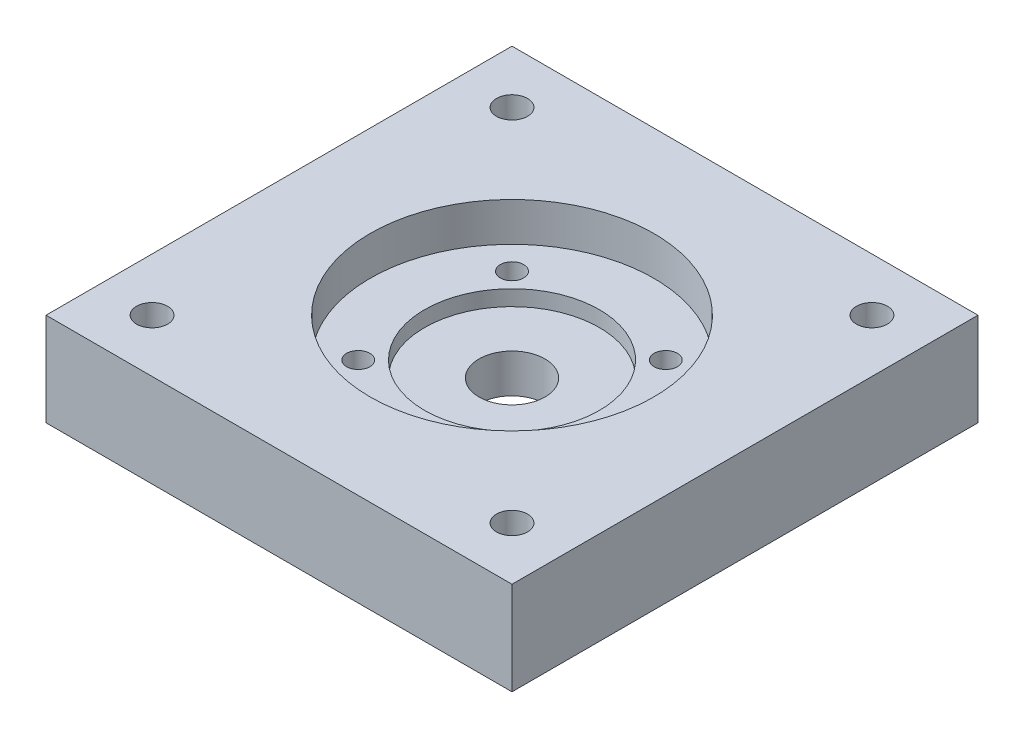
SolidWorks part; units mm, degrees
ref_plane "前视基准面" through (0, 0, 0) normal (0, 0, 1) x (1, 0, 0)
ref_plane "上视基准面" through (0, 0, 0) normal (0, 1, 0) x (1, 0, 0)
ref_plane "右视基准面" through (0, 0, 0) normal (1, 0, 0) x (0, 0, -1)
sketch "草图1" plane through (0, 0, 0) normal (0, 1, 0) x (1, 0, 0)
  line L0 (25.6208, 20.7218) -> (26.5174, 24.0679)
  line L1 (-21.05, 21.05) -> (21.05, 21.05)
  line L2 (-21.05, 21.05) -> (-21.05, -21.05)
  line L3 (-21.05, -21.05) -> (21.05, -21.05)
  line L4 (21.05, 21.05) -> (21.05, -21.05)
  line L5 (-21.05, 21.05) -> (21.05, -21.05) construction
  line L6 (-21.05, -21.05) -> (21.05, 21.05) construction
  line L7 (-30, 30) -> (30, 30)
  line L8 (-30, 30) -> (-30, -30)
  line L9 (-30, -30) -> (30, -30)
  line L10 (30, 30) -> (30, -30)
  line L11 (-30, 30) -> (30, -30) construction
  line L12 (-30, -30) -> (30, 30) construction
  line L13 (-20.7218, 25.6208) -> (-24.0679, 26.5174)
  line L14 (-24.0679, 26.5174) -> (-26.5174, 24.0679)
  line L15 (-26.5174, 24.0679) -> (-25.6208, 20.7218)
  line L16 (-25.6208, 20.7218) -> (-22.2747, 19.8253)
  line L17 (-22.2747, 19.8253) -> (-19.8253, 22.2747)
  line L18 (-19.8253, 22.2747) -> (-20.7218, 25.6208)
  line L19 (26.5174, 24.0679) -> (24.0679, 26.5174)
  line L20 (24.0679, 26.5174) -> (20.7218, 25.6208)
  line L21 (20.7218, 25.6208) -> (19.8253, 22.2747)
  line L22 (19.8253, 22.2747) -> (22.2747, 19.8253)
  line L23 (22.2747, 19.8253) -> (25.6208, 20.7218)
  line L24 (20.7218, -25.6208) -> (24.0679, -26.5174)
  line L25 (24.0679, -26.5174) -> (26.5174, -24.0679)
  line L26 (26.5174, -24.0679) -> (25.6208, -20.7218)
  line L27 (25.6208, -20.7218) -> (22.2747, -19.8253)
  line L28 (22.2747, -19.8253) -> (19.8253, -22.2747)
  line L29 (19.8253, -22.2747) -> (20.7218, -25.6208)
  line L30 (-25.6208, -20.7218) -> (-26.5174, -24.0679)
  line L31 (-26.5174, -24.0679) -> (-24.0679, -26.5174)
  line L32 (-24.0679, -26.5174) -> (-20.7218, -25.6208)
  line L33 (-20.7218, -25.6208) -> (-19.8253, -22.2747)
  line L34 (-19.8253, -22.2747) -> (-22.2747, -19.8253)
  line L35 (-22.2747, -19.8253) -> (-25.6208, -20.7218)
  circle A0 centre (0, 0) radius 14
  circle A1 centre (-9.8995, 9.8995) radius 1.5
  circle A2 centre (9.8995, 9.8995) radius 1.5
  circle A3 centre (9.8995, -9.8995) radius 1.5
  circle A4 centre (-9.8995, -9.8995) radius 1.5
  circle A5 centre (-23.1713, 23.1713) radius 2
  circle A6 centre (23.1713, 23.1713) radius 2
  circle A7 centre (-23.1713, -23.1713) radius 2
  circle A8 centre (23.1713, -23.1713) radius 2
  circle A9 centre (0, 0) radius 18.25
  circle A10 centre (-23.1713, 23.1713) radius 3 construction
  circle A11 centre (0, 0) radius 4.25
  circle A12 centre (0, 0) radius 11.25
  point P56 (0, 0)
  dimension "D1" = 28
  dimension "D3" = 3
  dimension "D5" = 4
  dimension "D6" = 36.5
  dimension "D8" = 3
  dimension "D11" = 8.5
  dimension "D12" = 22.5
  dimension "D2" = 42.1
  dimension "D4" = 60
  dimension "D7" = 6
  dimension "D9" = 45
  dimension "D10" = 4
extrude "凸台-拉伸1" add sketch "草图1" along normal blind 5 contours L10 L7 L8 L9 L35 L34 L2 L17 L16 L15 L14 L13 L18 L1 L22 L21 L20 L19 L0 L23 L4 L28 L27 L26 L25 L24 L29 L3 L33 L32 L31 L30 | L4 L1 L2 L3 A9 | A9 A4 A0 A1 A2 A3 | A4 A0 A3 A2 A1 A12 | A12 A11 | L17 L18 L13 L14 L15 L16 A5 | L22 L23 L0 L19 L20 L21 A6 | L34 L35 L30 L31 L32 L33 A7 | L28 L29 L24 L25 L26 L27 A8 region at (23.9233, 0, -20.365) region at (21.7293, 0, 20.5045) region at (-20.5045, 0, 21.7293) region at (-21.7293, 0, -20.5045) region at (20.4546, 0, 0) region at (0, 0, -29.1515) region at (12.8293, 0, 4.5252) region at (-17.7338, 0, 0) region at (-10.9318, 0, 0)
sketch "草图2" plane through (0, 5, 0) normal (0, 1, 0) x (1, 0, 0)
  line L4 (21.05, 21.05) -> (-21.05, 21.05)
  line L5 (21.05, -21.05) -> (21.05, 21.05)
  line L6 (-21.05, -21.05) -> (21.05, -21.05)
  line L7 (-21.05, 21.05) -> (-21.05, -21.05)
  line L8 (21.05, 21.05) -> (-21.05, 21.05)
  line L9 (21.05, -21.05) -> (21.05, 21.05)
  line L10 (-21.05, -21.05) -> (21.05, -21.05)
  line L11 (-21.05, 21.05) -> (-21.05, -21.05)
  line L12 (30, 30) -> (-30, 30)
  line L13 (30, -30) -> (30, 30)
  line L14 (-30, -30) -> (30, -30)
  line L15 (-30, 30) -> (-30, -30)
  line L16 (30, 30) -> (-30, 30)
  line L17 (30, -30) -> (30, 30)
  line L18 (-30, -30) -> (30, -30)
  line L19 (-30, 30) -> (-30, -30)
  line L22 (-25.6208, 20.7218) -> (-22.2747, 19.8253)
  line L23 (-22.2747, 19.8253) -> (-19.8253, 22.2747)
  line L24 (-19.8253, 22.2747) -> (-20.7218, 25.6208)
  line L25 (-20.7218, 25.6208) -> (-24.0679, 26.5174)
  line L26 (-24.0679, 26.5174) -> (-26.5174, 24.0679)
  line L27 (-26.5174, 24.0679) -> (-25.6208, 20.7218)
  line L28 (-25.6208, 20.7218) -> (-22.2747, 19.8253)
  line L29 (-22.2747, 19.8253) -> (-19.8253, 22.2747)
  line L30 (-19.8253, 22.2747) -> (-20.7218, 25.6208)
  line L31 (-20.7218, 25.6208) -> (-24.0679, 26.5174)
  line L32 (-24.0679, 26.5174) -> (-26.5174, 24.0679)
  line L33 (-26.5174, 24.0679) -> (-25.6208, 20.7218)
  line L34 (25.6208, 20.7218) -> (26.5174, 24.0679)
  line L35 (26.5174, 24.0679) -> (24.0679, 26.5174)
  line L36 (24.0679, 26.5174) -> (20.7218, 25.6208)
  line L37 (20.7218, 25.6208) -> (19.8253, 22.2747)
  line L38 (19.8253, 22.2747) -> (22.2747, 19.8253)
  line L39 (22.2747, 19.8253) -> (25.6208, 20.7218)
  line L40 (25.6208, 20.7218) -> (26.5174, 24.0679)
  line L41 (26.5174, 24.0679) -> (24.0679, 26.5174)
  line L42 (24.0679, 26.5174) -> (20.7218, 25.6208)
  line L43 (20.7218, 25.6208) -> (19.8253, 22.2747)
  line L44 (19.8253, 22.2747) -> (22.2747, 19.8253)
  line L45 (22.2747, 19.8253) -> (25.6208, 20.7218)
  line L46 (-25.6208, -20.7218) -> (-26.5174, -24.0679)
  line L47 (-26.5174, -24.0679) -> (-24.0679, -26.5174)
  line L48 (-24.0679, -26.5174) -> (-20.7218, -25.6208)
  line L49 (-20.7218, -25.6208) -> (-19.8253, -22.2747)
  line L50 (-19.8253, -22.2747) -> (-22.2747, -19.8253)
  line L51 (-22.2747, -19.8253) -> (-25.6208, -20.7218)
  line L52 (-25.6208, -20.7218) -> (-26.5174, -24.0679)
  line L53 (-26.5174, -24.0679) -> (-24.0679, -26.5174)
  line L54 (-24.0679, -26.5174) -> (-20.7218, -25.6208)
  line L55 (-20.7218, -25.6208) -> (-19.8253, -22.2747)
  line L56 (-19.8253, -22.2747) -> (-22.2747, -19.8253)
  line L57 (-22.2747, -19.8253) -> (-25.6208, -20.7218)
  line L58 (22.2747, -19.8253) -> (19.8253, -22.2747)
  line L59 (19.8253, -22.2747) -> (20.7218, -25.6208)
  line L60 (20.7218, -25.6208) -> (24.0679, -26.5174)
  line L61 (24.0679, -26.5174) -> (26.5174, -24.0679)
  line L62 (26.5174, -24.0679) -> (25.6208, -20.7218)
  line L63 (25.6208, -20.7218) -> (22.2747, -19.8253)
  line L64 (22.2747, -19.8253) -> (19.8253, -22.2747)
  line L65 (19.8253, -22.2747) -> (20.7218, -25.6208)
  line L66 (20.7218, -25.6208) -> (24.0679, -26.5174)
  line L67 (24.0679, -26.5174) -> (26.5174, -24.0679)
  line L68 (26.5174, -24.0679) -> (25.6208, -20.7218)
  line L69 (25.6208, -20.7218) -> (22.2747, -19.8253)
  circle A1 centre (-9.8995, -9.8995) radius 1.5
  circle A2 centre (-9.8995, -9.8995) radius 1.5
  circle A3 centre (9.8995, -9.8995) radius 1.5
  circle A4 centre (9.8995, -9.8995) radius 1.5
  circle A5 centre (9.8995, 9.8995) radius 1.5
  circle A6 centre (9.8995, 9.8995) radius 1.5
  circle A7 centre (-9.8995, 9.8995) radius 1.5
  circle A8 centre (-9.8995, 9.8995) radius 1.5
  circle A9 centre (0, 0) radius 14
  circle A10 centre (0, 0) radius 14
  circle A11 centre (0, 0) radius 4.25
  circle A12 centre (0, 0) radius 4.25
  circle A13 centre (0, 0) radius 18.25
  circle A14 centre (0, 0) radius 18.25
  circle A15 centre (23.1713, -23.1713) radius 2
  circle A16 centre (23.1713, -23.1713) radius 2
  circle A17 centre (-23.1713, -23.1713) radius 2
  circle A18 centre (-23.1713, -23.1713) radius 2
  circle A19 centre (23.1713, 23.1713) radius 2
  circle A20 centre (23.1713, 23.1713) radius 2
  circle A21 centre (-23.1713, 23.1713) radius 2
  circle A22 centre (-23.1713, 23.1713) radius 2
  circle A23 centre (0, 0) radius 11.25
  circle A24 centre (0, 0) radius 11.25
  circle M45 centre (-9.8995, -9.8995) radius 1.5
  circle M46 centre (-9.8995, 9.8995) radius 1.5
  circle M47 centre (9.8995, 9.8995) radius 1.5
  line M48 (30, -30) -> (30, 30)
  line M49 (30, 30) -> (-30, 30)
  line M50 (-30, 30) -> (-30, -30)
  line M51 (-30, -30) -> (30, -30)
  circle M56 centre (9.8995, -9.8995) radius 1.5
  dimension "D1" = 0
  dimension "D2" = 0
  dimension "D3" = 0
  dimension "D4" = 0
  dimension "D5" = 0
  dimension "D6" = 0
  dimension "D7" = 0
  dimension "D8" = 0
  dimension "D9" = 0
  dimension "D10" = 0
  dimension "D11" = 0
  dimension "D12" = 0
  dimension "D13" = 0
  dimension "D14" = 0
  dimension "D15" = 0
  dimension "D16" = 0
  dimension "D17" = 0
  dimension "D18" = 0
extrude "凸台-拉伸2" add sketch "草图2" along normal blind 2 contours L69 L68 L67 L66 L65 L64 L10 L56 L55 L54 L53 L52 L57 L11 L29 L28 L33 L32 L31 L30 L8 L44 L43 L42 L41 L40 L45 L9 M51 M48 M49 M50 | L8 L11 L10 L9 A14 | A10 A6 A8 A24 M56 M45 | A14 A10 A4 A2 M46 M47 | L40 L41 L42 L43 L44 L45 | L64 L65 L66 L67 L68 L69 | L52 L53 L54 L55 L56 L57 | L28 L29 L30 L31 L32 L33 | A20 | A16 | A18 | A22 region at (20.4546, 5, 0) region at (29.1515, 5, 0) region at (-9.1273, 5, 8.1679) region at (-17.7338, 5, 0)
sketch "草图3" plane through (0, 7, 0) normal (0, 1, 0) x (1, 0, 0)
  line L4 (21.05, 21.05) -> (-21.05, 21.05)
  line L5 (21.05, -21.05) -> (21.05, 21.05)
  line L6 (-21.05, -21.05) -> (21.05, -21.05)
  line L7 (-21.05, 21.05) -> (-21.05, -21.05)
  line L8 (21.05, 21.05) -> (-21.05, 21.05)
  line L9 (21.05, -21.05) -> (21.05, 21.05)
  line L10 (-21.05, -21.05) -> (21.05, -21.05)
  line L11 (-21.05, 21.05) -> (-21.05, -21.05)
  line L12 (30, 30) -> (-30, 30)
  line L13 (30, -30) -> (30, 30)
  line L14 (-30, -30) -> (30, -30)
  line L15 (-30, 30) -> (-30, -30)
  line L16 (30, 30) -> (-30, 30)
  line L17 (30, -30) -> (30, 30)
  line L18 (-30, -30) -> (30, -30)
  line L19 (-30, 30) -> (-30, -30)
  line L22 (-25.6208, 20.7218) -> (-22.2747, 19.8253)
  line L23 (-22.2747, 19.8253) -> (-19.8253, 22.2747)
  line L24 (-19.8253, 22.2747) -> (-20.7218, 25.6208)
  line L25 (-20.7218, 25.6208) -> (-24.0679, 26.5174)
  line L26 (-24.0679, 26.5174) -> (-26.5174, 24.0679)
  line L27 (-26.5174, 24.0679) -> (-25.6208, 20.7218)
  line L28 (-25.6208, 20.7218) -> (-22.2747, 19.8253)
  line L29 (-22.2747, 19.8253) -> (-19.8253, 22.2747)
  line L30 (-19.8253, 22.2747) -> (-20.7218, 25.6208)
  line L31 (-20.7218, 25.6208) -> (-24.0679, 26.5174)
  line L32 (-24.0679, 26.5174) -> (-26.5174, 24.0679)
  line L33 (-26.5174, 24.0679) -> (-25.6208, 20.7218)
  line L34 (25.6208, 20.7218) -> (26.5174, 24.0679)
  line L35 (26.5174, 24.0679) -> (24.0679, 26.5174)
  line L36 (24.0679, 26.5174) -> (20.7218, 25.6208)
  line L37 (20.7218, 25.6208) -> (19.8253, 22.2747)
  line L38 (19.8253, 22.2747) -> (22.2747, 19.8253)
  line L39 (22.2747, 19.8253) -> (25.6208, 20.7218)
  line L40 (25.6208, 20.7218) -> (26.5174, 24.0679)
  line L41 (26.5174, 24.0679) -> (24.0679, 26.5174)
  line L42 (24.0679, 26.5174) -> (20.7218, 25.6208)
  line L43 (20.7218, 25.6208) -> (19.8253, 22.2747)
  line L44 (19.8253, 22.2747) -> (22.2747, 19.8253)
  line L45 (22.2747, 19.8253) -> (25.6208, 20.7218)
  line L46 (-25.6208, -20.7218) -> (-26.5174, -24.0679)
  line L47 (-26.5174, -24.0679) -> (-24.0679, -26.5174)
  line L48 (-24.0679, -26.5174) -> (-20.7218, -25.6208)
  line L49 (-20.7218, -25.6208) -> (-19.8253, -22.2747)
  line L50 (-19.8253, -22.2747) -> (-22.2747, -19.8253)
  line L51 (-22.2747, -19.8253) -> (-25.6208, -20.7218)
  line L52 (-25.6208, -20.7218) -> (-26.5174, -24.0679)
  line L53 (-26.5174, -24.0679) -> (-24.0679, -26.5174)
  line L54 (-24.0679, -26.5174) -> (-20.7218, -25.6208)
  line L55 (-20.7218, -25.6208) -> (-19.8253, -22.2747)
  line L56 (-19.8253, -22.2747) -> (-22.2747, -19.8253)
  line L57 (-22.2747, -19.8253) -> (-25.6208, -20.7218)
  line L58 (22.2747, -19.8253) -> (19.8253, -22.2747)
  line L59 (19.8253, -22.2747) -> (20.7218, -25.6208)
  line L60 (20.7218, -25.6208) -> (24.0679, -26.5174)
  line L61 (24.0679, -26.5174) -> (26.5174, -24.0679)
  line L62 (26.5174, -24.0679) -> (25.6208, -20.7218)
  line L63 (25.6208, -20.7218) -> (22.2747, -19.8253)
  line L64 (22.2747, -19.8253) -> (19.8253, -22.2747)
  line L65 (19.8253, -22.2747) -> (20.7218, -25.6208)
  line L66 (20.7218, -25.6208) -> (24.0679, -26.5174)
  line L67 (24.0679, -26.5174) -> (26.5174, -24.0679)
  line L68 (26.5174, -24.0679) -> (25.6208, -20.7218)
  line L69 (25.6208, -20.7218) -> (22.2747, -19.8253)
  circle A1 centre (-9.8995, -9.8995) radius 1.5
  circle A2 centre (-9.8995, -9.8995) radius 1.5
  circle A3 centre (9.8995, -9.8995) radius 1.5
  circle A4 centre (9.8995, -9.8995) radius 1.5
  circle A5 centre (9.8995, 9.8995) radius 1.5
  circle A6 centre (9.8995, 9.8995) radius 1.5
  circle A7 centre (-9.8995, 9.8995) radius 1.5
  circle A8 centre (-9.8995, 9.8995) radius 1.5
  circle A9 centre (0, 0) radius 14
  circle A10 centre (0, 0) radius 14
  circle A11 centre (0, 0) radius 4.25
  circle A12 centre (0, 0) radius 4.25
  circle A13 centre (0, 0) radius 18.25
  circle A14 centre (0, 0) radius 18.25
  circle A15 centre (23.1713, -23.1713) radius 2
  circle A16 centre (23.1713, -23.1713) radius 2
  circle A17 centre (-23.1713, -23.1713) radius 2
  circle A18 centre (-23.1713, -23.1713) radius 2
  circle A19 centre (23.1713, 23.1713) radius 2
  circle A20 centre (23.1713, 23.1713) radius 2
  circle A21 centre (-23.1713, 23.1713) radius 2
  circle A22 centre (-23.1713, 23.1713) radius 2
  circle A23 centre (0, 0) radius 11.25
  circle A24 centre (0, 0) radius 11.25
  line M72 (-30, -30) -> (30, -30)
  line M73 (30, -30) -> (30, 30)
  line M74 (30, 30) -> (-30, 30)
  line M75 (-30, 30) -> (-30, -30)
  dimension "D1" = 0
  dimension "D2" = 0
  dimension "D3" = 0
  dimension "D4" = 0
  dimension "D5" = 0
  dimension "D6" = 0
  dimension "D7" = 0
  dimension "D8" = 0
  dimension "D9" = 0
  dimension "D10" = 0
  dimension "D11" = 0
  dimension "D12" = 0
  dimension "D13" = 0
  dimension "D14" = 0
  dimension "D15" = 0
  dimension "D16" = 0
  dimension "D17" = 0
  dimension "D18" = 0
extrude "凸台-拉伸3" add sketch "草图3" along normal blind 5 contours L11 L8 L9 L10 M75 M72 M73 M74 | L8 L11 L10 L9 A14 | L64 L65 L66 L67 L68 L69 | A16 | L52 L53 L54 L55 L56 L57 | A18 | L28 L29 L30 L31 L32 L33 | A22 | L40 L41 L42 L43 L44 L45 | A20 region at (20.4546, 7, 0) region at (29.1515, 7, 0)
